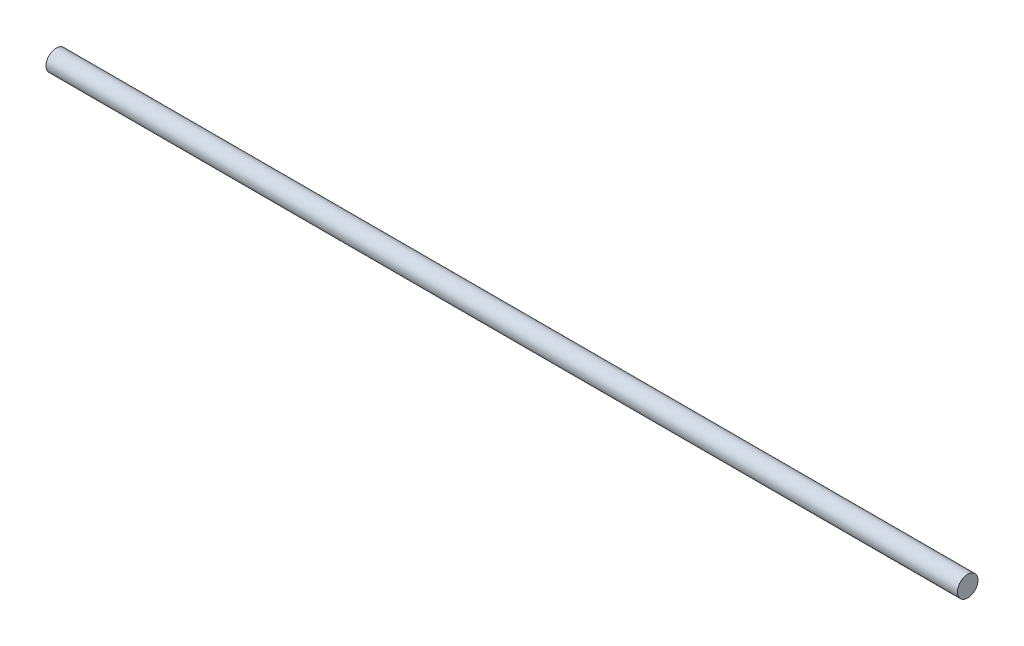
SolidWorks part; units mm, degrees
ref_plane "Front Plane" through (0, 0, 0) normal (0, 0, 1) x (1, 0, 0)
ref_plane "Top Plane" through (0, 0, 0) normal (0, 1, 0) x (1, 0, 0)
ref_plane "Right Plane" through (0, 0, 0) normal (1, 0, 0) x (0, 0, -1)
sketch "Sketch1" plane through (0, 0, 0) normal (1, 0, 0) x (0, 0, -1)
  circle A0 centre (0, 0) radius 1.505
  dimension "D1" = 3.0099
extrude "Boss-Extrude1" add sketch "Sketch1" along normal mid plane 133.35
